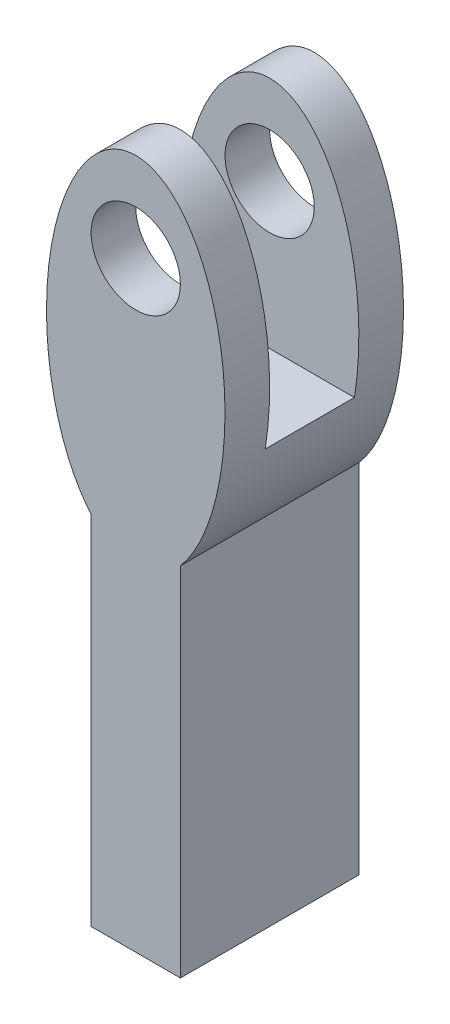
SolidWorks part; units mm, degrees
material "1060 Alloy"
ref_plane "Front" through (0, 0, 0) normal (0, 0, 1) x (1, 0, 0)
ref_plane "Top" through (0, 0, 0) normal (0, 1, 0) x (1, 0, 0)
ref_plane "Right" through (0, 0, 0) normal (1, 0, 0) x (0, 0, -1)
sketch "Sketch3" plane through (0, 0, 0) normal (0, 0, 1) x (1, 0, 0)
  line L2 (-12.7, -43.9941) -> (-12.7, -145.5941)
  line L3 (-12.7, -145.5941) -> (12.7, -145.5941)
  line L4 (12.7, -43.9941) -> (12.7, -145.5941)
  ellipse E0 centre (0, 0) end of major axis (0, -50.8) minor radius 25.4 (12.7, -43.9941) -> (-12.7, -43.9941) ccw
  dimension "D1" = 50.8
  dimension "D2" = 101.6
  dimension "D3" = 25.4
  dimension "D4" = 101.6
extrude "Boss-Extrude1" add sketch "Sketch3" along normal blind 25.4 and the other way blind 25.4
sketch "Sketch4" plane through (0, 0, 25.4) normal (0, 0, 1) x (1, 0, 0)
  circle A0 centre (0, 25.4) radius 12.7
  ellipse E0 centre (0, 0) end of major axis (0, -50.8) minor radius 25.4 (12.7, -43.9941) -> (-12.7, -43.9941) ccw construction
  dimension "D1" = 25.4
  dimension "D2" = 25.4
extrude "Cut-Extrude1" cut sketch "Sketch4" against normal up to next
sketch "Sketch5" plane through (0, 0, 0) normal (0, 0, 1) x (1, 0, 0)
  line L0 (-24.13, -15.8623) -> (24.13, -15.8623)
  ellipse E0 centre (0, 0) end of major axis (0, -50.8) minor radius 25.4 (24.13, -15.8623) -> (-24.13, -15.8623) ccw
  ellipse E1 centre (0, 0) end of major axis (0, -50.8) minor radius 25.4 (12.7, -43.9941) -> (-12.7, -43.9941) ccw construction
  dimension "D1" = 48.26
extrude "Cut-Extrude2" cut sketch "Sketch5" against normal blind 12.7 and the other way blind 12.7
